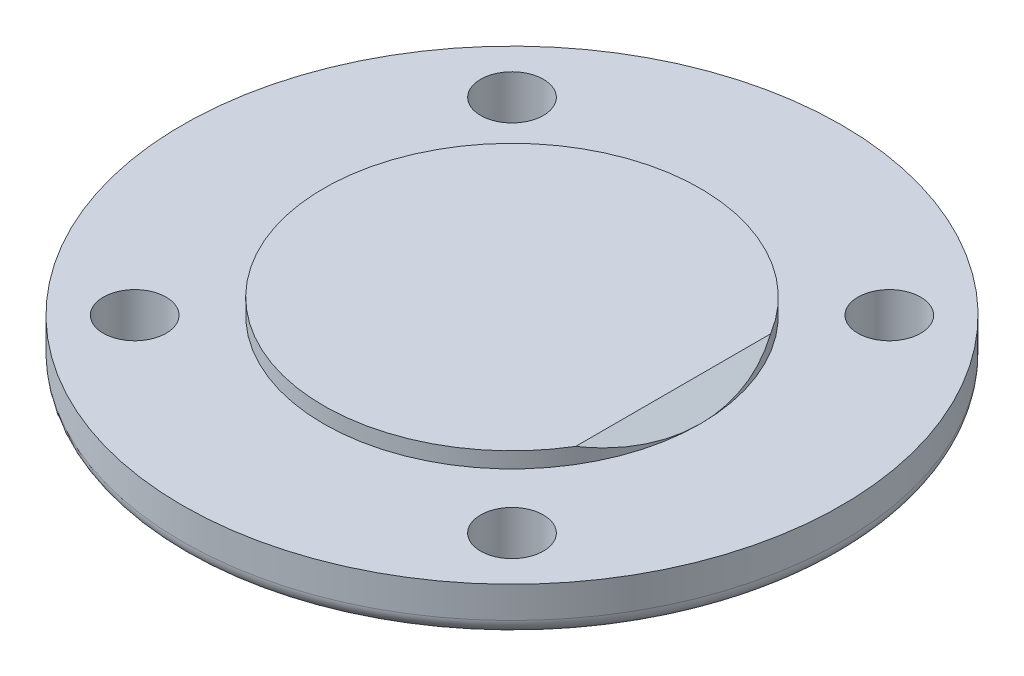
SolidWorks part; units mm, degrees
ref_plane "Front Plane" through (0, 0, 0) normal (0, 0, 1) x (1, 0, 0)
ref_plane "Top Plane" through (0, 0, 0) normal (0, 1, 0) x (1, 0, 0)
ref_plane "Right Plane" through (0, 0, 0) normal (1, 0, 0) x (0, 0, -1)
sketch "Sketch1" plane through (0, 0, 0) normal (0, 1, 0) x (1, 0, 0)
  circle A0 centre (0, 0) radius 21
  dimension "D1" = 42
extrude "Boss-Extrude1" add sketch "Sketch1" along normal blind 3
sketch "Sketch2" plane through (0, 3, 0) normal (0, 1, 0) x (1, 0, 0)
  circle A0 centre (0, 0) radius 12
  dimension "D1" = 24
extrude "Boss-Extrude2" add sketch "Sketch2" along normal blind 1
extrude "Cut-Extrude1" cut sketch "Sketch2<2>" along normal blind 1 from offset 3 offset against normal yes
sketch "Sketch2<2>" plane through (0, 3, 0) normal (0, 1, 0) x (1, 0, 0) same geometry as "Sketch2"
sketch "Sketch3" plane through (0, 3, 0) normal (0, 1, 0) x (1, 0, 0)
  line L0 (0, 21) -> (0, 0) construction
  line L1 (0, 0) -> (12.0208, 12.0208) construction
  circle A0 centre (0, 0) radius 17 construction
  circle A1 centre (12.0208, 12.0208) radius 2
  circle A2 centre (0, 0) radius 21 construction
  dimension "D1" = 34
  dimension "D3" = 4
  dimension "D2" = 45
extrude "Cut-Extrude2" cut sketch "Sketch3" against normal through all
pattern_circular "CirPattern1" count 4 over 360 about axis through (0, 3, 0) along (0, -1, 0) of "Cut-Extrude2" reverse direction yes
fillet "Fillet1" radius 1 1 edges at (0, 0, 21)
sketch "Sketch4" plane through (0, 0, 0) normal (0, 0, 1) x (1, 0, 0)
  line L0 (12, 3) -> (10.2679, 4)
  line L1 (12, 4) -> (-12, 4) construction
  line L2 (10.2679, 4) -> (12, 4)
  line L3 (12, 4) -> (12, 3)
  line L4 (21, 3) -> (-21, 3) construction
  dimension "D1" = 30
extrude "Cut-Extrude3" cut sketch "Sketch4" against normal mid plane 71
